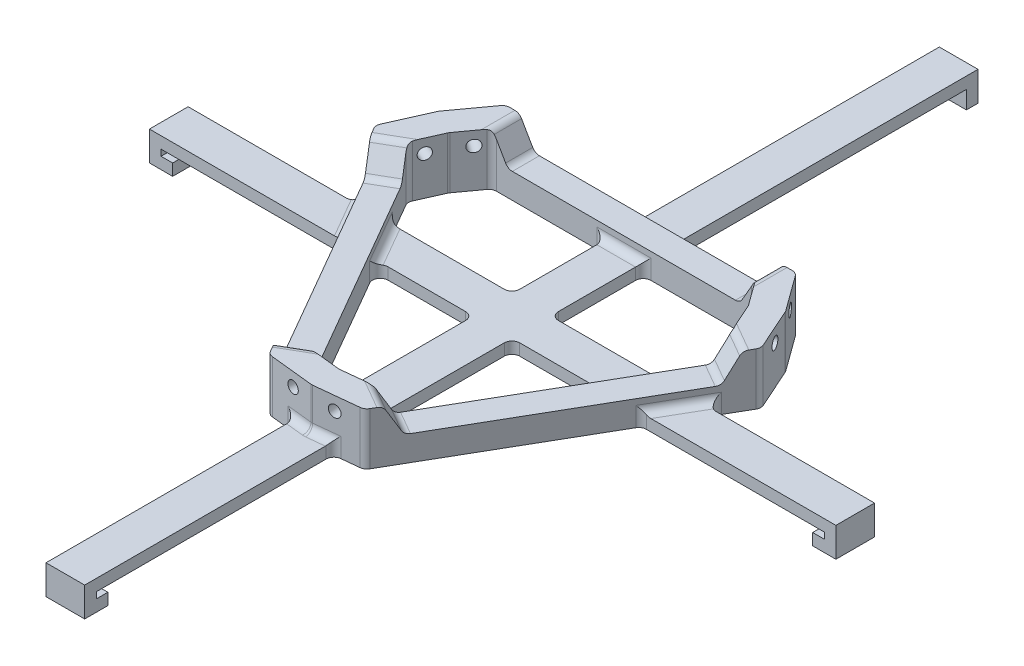
SolidWorks part; units mm, degrees
ref_plane "Front" through (0, 0, 0) normal (0, 0, 1) x (1, 0, 0)
ref_plane "Top" through (0, 0, 0) normal (0, 1, 0) x (1, 0, 0)
ref_plane "Right" through (0, 0, 0) normal (1, 0, 0) x (0, 0, -1)
sketch "Эскиз1" plane through (0, 0, 0) normal (0, 1, 0) x (1, 0, 0)
  line L0 (-8.6603, 5) -> (-51.9615, 30) construction
  line L4 (0, -60) -> (51.9615, 30) construction
  line L5 (51.9615, 30) -> (-51.9615, 30) construction
  line L6 (-51.9615, 30) -> (0, -60) construction
  line L7 (8.6603, 5) -> (51.9615, 30) construction
  line L8 (0, 0) -> (0, -50) construction
  line L9 (0, 0) -> (-41.6644, 30.2709)
  line L10 (0, 0) -> (-47.0476, 20.9469)
  line L11 (0, 0) -> (48.541, 35.2671)
  line L13 (54.8127, 24.4042) -> (0, 0)
  line L14 (0, 0) -> (-6.2717, -59.6713)
  line L16 (6.2717, -59.6713) -> (0, 0)
  line L17 (-49.8947, 14.5521) -> (-44.846, 25.8918)
  line L18 (-44.846, 25.8918) -> (-37.5499, 35.9341)
  line L27 (-47.6577, 19.5766) -> (-29.7377, 11.5981)
  line L28 (-40.7827, 31.4845) -> (-29.024, 22.9413)
  line L45 (0, 0) -> (-60.0777, 0) construction
  line L91 (37.5499, 35.9341) -> (44.846, 25.8918)
  line L98 (44.846, 25.8918) -> (49.8947, 14.5521)
  line L101 (40.7827, 31.4845) -> (24.9131, 19.9545)
  line L107 (47.6577, 19.5766) -> (34.3797, 13.6649)
  line L121 (12.3449, -50.4862) -> (0, -51.7837)
  line L122 (0, -51.7837) -> (-12.3449, -50.4862)
  line L123 (6.875, -51.0611) -> (4.8246, -31.5526)
  line L124 (-6.875, -51.0611) -> (-5.3557, -36.6062)
  line L125 (37.5499, 35.9341) -> (-37.5499, 35.9341)
  line L126 (-49.8947, 14.5521) -> (-12.3449, -50.4862)
  line L127 (12.3449, -50.4862) -> (49.8947, 14.5521)
  line L131 (8.066, -43.8973) -> (42.0492, 14.9633)
  line L132 (38.7504, 22.3726) -> (42.0492, 14.9633)
  line L133 (33.9832, 28.9341) -> (38.7504, 22.3726)
  line L134 (33.9832, 28.9341) -> (-33.9832, 28.9341)
  line L135 (-38.7504, 22.3726) -> (-33.9832, 28.9341)
  line L136 (-42.0492, 14.9633) -> (-38.7504, 22.3726)
  line L137 (-42.0492, 14.9633) -> (-8.066, -43.8973)
  line L138 (0, -44.7451) -> (-8.066, -43.8973)
  line L139 (8.066, -43.8973) -> (0, -44.7451)
  circle A1 centre (0, 0) radius 60 construction
  circle A2 centre (0, 0) radius 51.5 construction
  point P21 (0, 0)
  point P44 (-0.2291, 0.1323)
  point P47 (-4.0451, 2.3354)
  point P49 (0, 0)
  point P69 (-0.0303, 0.0175)
  point P90 (2.4271, -1.4013)
  dimension "D1" = 120
  dimension "D9" = 8.5
  dimension "D10" = 103
  dimension "D11" = 7
  dimension "D14" = 1.5
  dimension "D17" = 108
  dimension "D2" = 6
  dimension "D3" = 6
  dimension "D4" = 10.7664
  dimension "D5" = 6
  dimension "D6" = 6
  dimension "D7" = 3
  dimension "D8" = 6
  dimension "D12" = 7
  dimension "D13" = 7
extrude "Бобышка-Вытянуть1" add sketch "Эскиз1" along normal blind 3.5 and the other way blind 10 contours L10 L136 L135 L9 L18 L17 | L9 L135 L28 L18 | L134 L133 L101 L91 L125 L18 L28 L135 | L11 L133 L132 L13 L98 L91 | L101 L133 L11 L91 | L13 L132 L107 L98 | L131 L139 L123 L121 L127 L98 L107 L132 | L123 L139 L16 L121 | L16 L139 L138 L14 L122 L121 | L14 L138 L124 L122 | L137 L136 L27 L17 L126 L122 L124 L138 | L27 L136 L10 L17 region at (-41.6435, 0, -24.0429) region at (-38.392, 0, -28.8205) region at (-44.1552, 0, -18.8382) region at (38.392, 0, -28.8205) region at (41.6435, 0, -24.0429) region at (44.1552, 0, -18.8382) region at (0, 0, 48.0858) region at (-5.7633, 0, 47.6587) region at (5.7633, 0, 47.6587) region at (0, 0, -32.3871) region at (-28.048, 0, 16.1935) region at (28.048, 0, 16.1935)
revolve "Вырез-Повернуть1" cut sketch "Эскиз1<3>" angle 360 about L10 region at (-44.1552, 0, -18.8382)
sketch "Эскиз1<3>" plane through (0, 0, 0) normal (0, 1, 0) x (1, 0, 0) same geometry as "Эскиз1"
revolve "Вырез-Повернуть2" cut sketch "Эскиз1<4>" angle 360 about L9 region at (-38.392, 0, -28.8205)
sketch "Эскиз1<4>" plane through (0, 0, 0) normal (0, 1, 0) x (1, 0, 0) same geometry as "Эскиз1"
ref_axis "Ось1" through (0, 0, 0) along (0, -1, 0)
pattern_circular "Круговой массив1" count 3 over 360 about axis through (0, 0, 0) along (0, -1, 0) of "Вырез-Повернуть2", "Вырез-Повернуть1" reverse direction yes
sketch "Эскиз2" plane through (0, 0, 0) normal (0, 0, 1) x (1, 0, 0)
  line L0 (0, 0) -> (0, -7)
  line L2 (0, -7) -> (88.75, -7)
  line L3 (88.75, -7) -> (88.75, -14.6)
  line L4 (88.75, -14.6) -> (82.75, -14.6)
  line L5 (82.75, -14.6) -> (82.75, -11.6)
  line L6 (82.75, -11.6) -> (85.75, -11.6)
  line L7 (85.75, -11.6) -> (85.75, -10)
  line L8 (85.75, -10) -> (0, -10)
  line L9 (0, -4.9424) -> (0, 4.9424) construction
  line L10 (0, -10) -> (0, -7)
  line L11 (0, -7) -> (-88.75, -7)
  line L12 (-88.75, -7) -> (-88.75, -14.6)
  line L13 (-88.75, -14.6) -> (-82.75, -14.6)
  line L14 (-82.75, -14.6) -> (-82.75, -11.6)
  line L15 (-82.75, -11.6) -> (-85.75, -11.6)
  line L16 (-85.75, -10) -> (-85.75, -11.6)
  line L17 (0, -10) -> (-85.75, -10)
  line L18 (0, -10) -> (0, 3.5) construction
  dimension "D1" = 3
  dimension "D2" = 1.6
  dimension "D3" = 1.6
  dimension "D4" = 171.5
  dimension "D5" = 85.75
  dimension "D6" = 3
  dimension "D7" = 3
  dimension "D8" = 3
  dimension "D9" = 6
  dimension "D10" = 3
  dimension "D11" = 3
  dimension "D12" = 7
extrude "Бобышка-Вытянуть2" add sketch "Эскиз2" along normal mid plane 10 contours L10 L8 L7 L6 L5 L4 L3 L2 | L17 L10 L11 L12 L13 L14 L15 L16 region at (47.6635, -8.8246, 0) region at (-47.6635, -8.8246, 0)
sketch "Эскиз4" plane through (0, 0, 0) normal (1, 0, 0) x (0, 0, -1)
  line L0 (0, 0) -> (0, -7)
  line L1 (0, -7) -> (115.5, -7)
  line L2 (115.5, -7) -> (115.5, -14.6)
  line L3 (115.5, -14.6) -> (109.5, -14.6)
  line L4 (109.5, -14.6) -> (109.5, -11.6)
  line L5 (109.5, -11.6) -> (112.5, -11.6)
  line L6 (112.5, -11.6) -> (112.5, -10)
  line L7 (112.5, -10) -> (0, -10)
  line L8 (0, -10) -> (0, -7)
  line L9 (0, -7) -> (-115.5, -7)
  line L10 (-115.5, -7) -> (-115.5, -14.6)
  line L11 (-115.5, -14.6) -> (-109.5, -14.6)
  line L12 (-109.5, -14.6) -> (-109.5, -11.6)
  line L13 (-109.5, -11.6) -> (-112.5, -11.6)
  line L14 (-112.5, -10) -> (-112.5, -11.6)
  line L15 (0, -10) -> (-112.5, -10)
  line L16 (112.5, -11.6) -> (112.5, -28.6227)
  dimension "D1" = 3
  dimension "D2" = 1.6
  dimension "D3" = 1.6
  dimension "D4" = 225
  dimension "D5" = 112.5
  dimension "D6" = 3
  dimension "D7" = 3
  dimension "D8" = 3
  dimension "D9" = 6
  dimension "D10" = 3
  dimension "D11" = 3
  dimension "D12" = 7
extrude "Бобышка-Вытянуть3" add sketch "Эскиз4" along normal mid plane 10 contours L15 L8 L9 L10 L11 L12 L13 L14 | L8 L7 L6 L5 L4 L3 L2 L1 region at (0, -8.6455, -59.9045) region at (0, -8.7541, 61.1497)
sketch "Эскиз5" plane through (0, 0, 0) normal (0, 0, 1) x (1, 0, 0)
  line L0 (0, 0) -> (0, -3.5)
  line L1 (0, -4.9424) -> (0, 4.9424) construction
  line L2 (0, -3.5) -> (30, -3.5)
  line L3 (30, -3.5) -> (38.757, 11.6676)
  line L4 (0, -3.5) -> (-30, -3.5)
  line L5 (-30, -3.5) -> (-39.3199, 12.6425)
  line L6 (38.757, 11.6676) -> (-39.3199, 12.6425)
  dimension "D1" = 3.5
  dimension "D2" = 30
  dimension "D3" = 120
  dimension "D4" = 30
  dimension "D5" = 120
extrude "Вырез-Вытянуть1" cut sketch "Эскиз5" against normal through all from offset 10 contours L3 L6 L5 L4 L2 region at (-0.4583, 4.671, 0) offset against normal yes
pattern_circular "Круговой массив2" count 3 over 360 about axis through (0, 0, 0) along (0, -1, 0) of "Вырез-Вытянуть1"
fillet "Скругление1" radius 2 17 edges at (5, -8.5, 51.2582) (-44.3798, -8.5, -5) (-38.6063, -8.5, 5) (-5, -8.5, 51.2582) (12.3449, -3.25, 50.4862) (0, -1.75, 51.7837) (-12.3449, -3.25, 50.4862) (-49.8947, -3.25, -14.5521) (-44.846, -3.25, -25.8918) (-37.5499, -3.25, -35.9341) (37.5499, -3.25, -35.9341) (44.846, -3.25, -25.8918) (49.8947, -3.25, -14.5521) (38.6063, -8.5, 5) (44.3798, -8.5, -5) (5, -8.5, -35.9341) (-5, -8.5, -35.9341)
fillet "Скругление2" radius 2 21 edges at (30.5234, -8.5, 5) (-36.2969, -8.5, -5) (-30.5234, -8.5, 5) (-33.9832, -3.3004, -28.9341) (-38.7504, -3.25, -22.3726) (-42.0492, -3.3004, -14.9633) (-8.066, -3.3004, 43.8973) (0, -1.75, 44.7451) (8.066, -3.3004, 43.8973) (33.9832, -3.3004, -28.9341) (38.7504, -3.25, -22.3726) (42.0492, -3.3004, -14.9633) (36.2969, -8.5, -5) (5, -8.5, 44.2196) (-5, -8.5, 44.2196) (-5, -8.5, 5) (5, -8.5, 5) (5, -8.5, -28.9341) (5, -8.5, -5) (-5, -8.5, -5) (-5, -8.5, -28.9341)
fillet "Скругление3" radius 2 14 edges at (-3.5, -7, 51.4158) (0, -7, 51.7727) (7.0917, -7, 43.9994) (3.6308, -7, 44.3635) (0, -7, 44.7341) (-7.0917, -7, 43.9994) (3.5, -7, 51.4158) (-32.8328, -7, 1) (-3.6308, -7, 44.3635) (0, -7, -28.9341) (42.0704, -7, -1) (32.8328, -7, 1) (-42.0704, -7, -1) (0, -7, -35.9341)
fillet "Скругление4" radius 2 12 edges at (30, -3.5, -32.4341) (34.0415, 3.5, -32.2766) (43.0887, -3.5, -9.7637) (44.9731, 3.5, -13.3425) (13.0887, -3.5, 42.1978) (10.9316, 3.5, 45.6191) (-10.9316, 3.5, 45.6191) (-13.0887, -3.5, 42.1978) (-43.0887, -3.5, -9.7637) (-44.9731, 3.5, -13.3425) (-30, -3.5, -32.4341) (-34.0415, 3.5, -32.2766)
